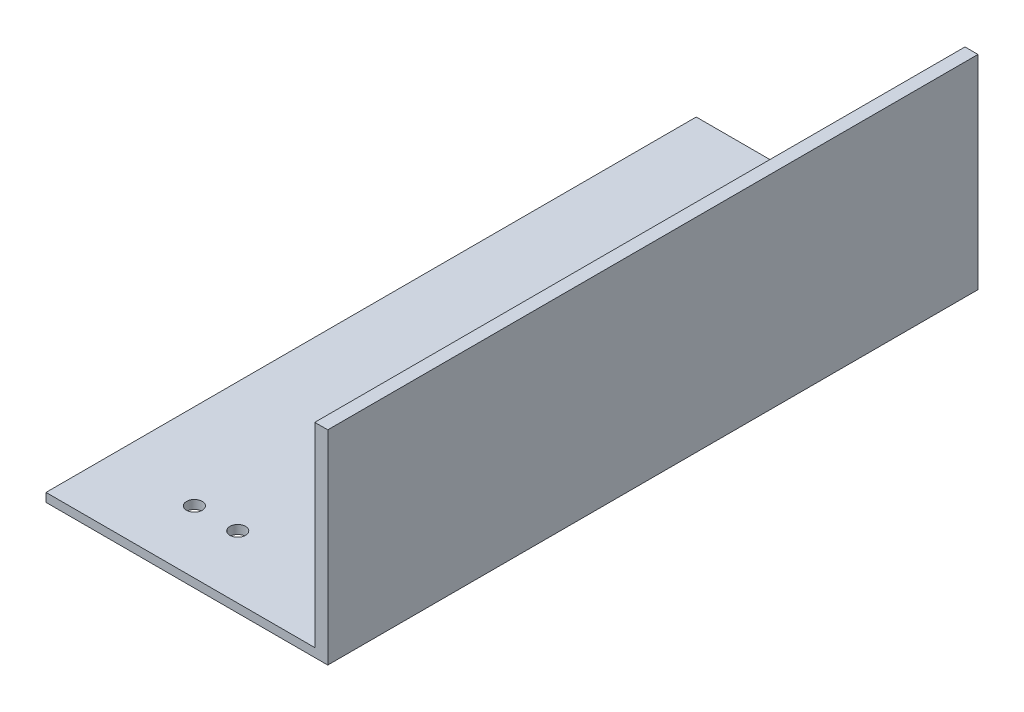
SolidWorks part; units mm, degrees
ref_plane "Alzado" through (0, 0, 0) normal (0, 0, 1) x (1, 0, 0)
ref_plane "Planta" through (0, 0, 0) normal (0, 1, 0) x (1, 0, 0)
ref_plane "Vista lateral" through (0, 0, 0) normal (1, 0, 0) x (0, 0, -1)
sketch "Croquis1" plane through (0, 0, 0) normal (0, 1, 0) x (1, 0, 0)
  line L0 (32.5, 12.25) -> (-32.5, 12.25) construction
  line L1 (32.5, 75) -> (-32.5, 75)
  line L2 (32.5, 75) -> (32.5, -75)
  line L3 (32.5, -75) -> (-32.5, -75)
  line L4 (-32.5, 75) -> (-32.5, -75)
  line L5 (32.5, 75) -> (-32.5, -75) construction
  line L6 (32.5, -75) -> (-32.5, 75) construction
  line L7 (32.5, 0) -> (-32.5, 0) construction
  line L8 (32.5, 60.57) -> (-32.5, 60.57) construction
  line L9 (-2.7, 12.25) -> (-2.7, 60.57) construction
  line L10 (-12.7, 12.25) -> (-12.7, 60.57) construction
  circle A0 centre (-2.7, 12.25) radius 1.8
  circle A1 centre (-2.7, 60.57) radius 1.8
  circle A2 centre (-12.7, -60.57) radius 1.8
  circle A3 centre (-2.7, -60.57) radius 1.8
  circle A4 centre (-12.7, 12.25) radius 1.8
  circle A5 centre (-12.7, 60.57) radius 1.8
  circle A6 centre (-12.7, -12.25) radius 1.8
  circle A7 centre (-2.7, -12.25) radius 1.8
  point P0 (0, 0)
  point P1 (0, 0)
  dimension "D3" = 10
  dimension "D4" = 3.6
  dimension "D5" = 19.8
  dimension "D1" = 150
  dimension "D2" = 65
  dimension "D6" = 48.32
  dimension "D8" = 12.25
extrude "Saliente-Extruir1" add sketch "Croquis1" along normal blind 2
sketch "Croquis2" plane through (0, 2, 0) normal (0, 1, 0) x (1, 0, 0)
  line L1 (32.5, 75) -> (29.5, 75)
  line L2 (32.5, 75) -> (32.5, -75)
  line L3 (32.5, -75) -> (29.5, -75)
  line L4 (29.5, 75) -> (29.5, -75)
  dimension "D1" = 3
extrude "Saliente-Extruir2" add sketch "Croquis2" along normal blind 45
